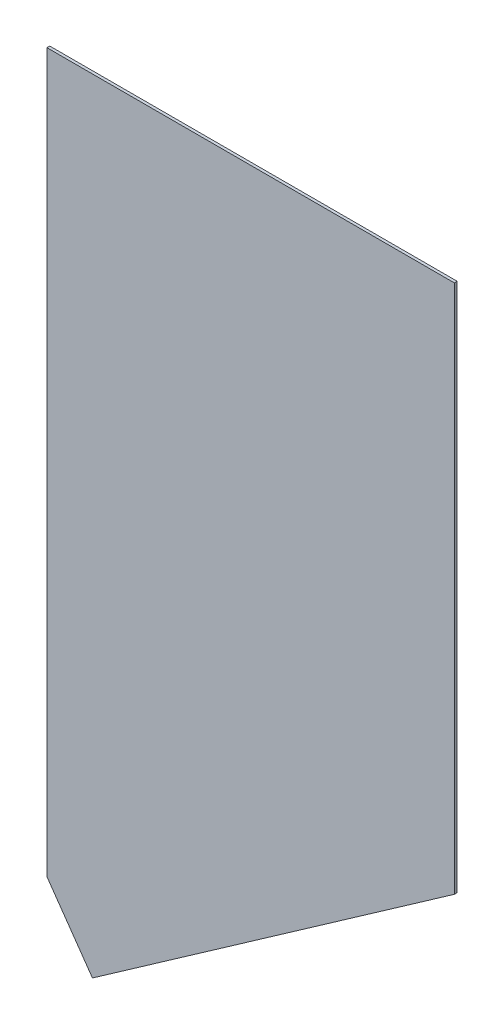
SolidWorks part; units mm, degrees
material "Acrylic (Medium-high impact)"
ref_plane "Front Plane" through (0, 0, 0) normal (0, 0, 1) x (1, 0, 0)
ref_plane "Top Plane" through (0, 0, 0) normal (0, 1, 0) x (1, 0, 0)
ref_plane "Right Plane" through (0, 0, 0) normal (1, 0, 0) x (0, 0, -1)
sketch "Sketch1" plane through (0, 0, 0) normal (0, 0, 1) x (1, 0, 0)
  line L1 (-50.8, 0) -> (254, 0)
  line L2 (-50.8, 0) -> (-50.8, -635)
  line L3 (-50.8, -635) -> (254, -635)
  line L4 (254, 0) -> (254, -635)
extrude "Boss-Extrude1" add sketch "Sketch1" along normal blind 2.1082
sketch "Sketch2" plane through (0, 0, 2.1082) normal (0, 0, 1) x (1, 0, 0)
  line L0 (-50.8, -537.0501) -> (-16.7127, -585.7318)
  line L2 (-16.7127, -585.7318) -> (255.7234, -394.97)
  line L4 (255.7234, -394.97) -> (255.7234, -635)
  line L5 (255.7234, -635) -> (-50.8, -635)
  line L8 (-50.8, -635) -> (-50.8, -537.0501)
  point P4 (0, 0)
  point P5 (257.3951, -393.7994)
  point P8 (257.0245, -394.0589)
extrude "Cut-Extrude1" cut sketch "Sketch2" against normal blind 2.1082
